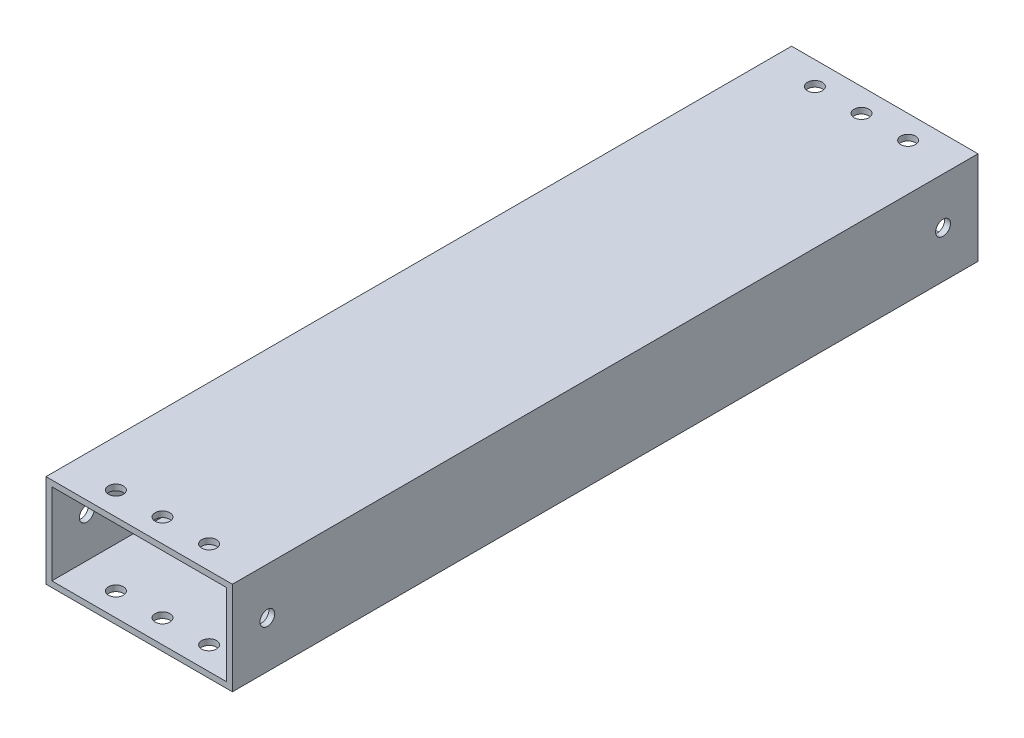
SolidWorks part; units mm, degrees
ref_plane "Front Plane" through (0, 0, 0) normal (0, 0, 1) x (1, 0, 0)
ref_plane "Top Plane" through (0, 0, 0) normal (0, 1, 0) x (1, 0, 0)
ref_plane "Right Plane" through (0, 0, 0) normal (1, 0, 0) x (0, 0, -1)
sketch "Sketch1" plane through (0, 0, 0) normal (0, 0, 1) x (1, 0, 0)
  line L0 (-23.8125, 11.1125) -> (23.8125, 11.1125)
  line L1 (-25.4, -12.7) -> (25.4, -12.7)
  line L2 (-25.4, -12.7) -> (-25.4, 12.7)
  line L3 (-25.4, 12.7) -> (25.4, 12.7)
  line L4 (25.4, -12.7) -> (25.4, 12.7)
  line L5 (-25.4, -12.7) -> (25.4, 12.7) construction
  line L6 (-25.4, 12.7) -> (25.4, -12.7) construction
  line L7 (23.8125, -11.1125) -> (23.8125, 11.1125)
  line L8 (-23.8125, -11.1125) -> (23.8125, -11.1125)
  line L9 (-23.8125, -11.1125) -> (-23.8125, 11.1125)
  point P0 (0, 0)
  dimension "D1" = 50.8
  dimension "D2" = 25.4
  dimension "D3" = 1.5875
extrude "Boss-Extrude1" add sketch "Sketch1" along normal mid plane 203.2
sketch "Sketch2" plane through (25.4, 0, 0) normal (1, 0, 0) x (0, 0, -1)
  line L0 (-101.6, -12.7) -> (-101.6, 12.7) construction
  line L1 (0, 12.7) -> (0, -12.7) construction
  line L2 (-101.6, 12.7) -> (101.6, 12.7) construction
  line L3 (-101.6, -12.7) -> (101.6, -12.7) construction
  circle A0 centre (-92.075, 0) radius 2.0193
  circle A1 centre (92.075, 0) radius 2.0193
  point P10 (0, 0)
  dimension "D2" = 4.0386
  dimension "D1" = 9.525
extrude "Cut-Extrude1" cut sketch "Sketch2" against normal through all
sketch "Sketch3" plane through (0, 12.7, 0) normal (0, 1, 0) x (1, 0, 0)
  line L0 (-25.4, 0) -> (25.4, 0) construction
  line L1 (-25.4, -101.6) -> (-25.4, 101.6) construction
  line L2 (25.4, -101.6) -> (25.4, 101.6) construction
  line L3 (25.4, -101.6) -> (-25.4, -101.6) construction
  circle A0 centre (-12.7, -95.25) radius 2.0193
  circle A1 centre (0, -95.25) radius 2.0193
  circle A2 centre (12.7, -95.25) radius 2.0193
  circle A3 centre (12.7, 95.25) radius 2.0193
  circle A4 centre (0, 95.25) radius 2.0193
  circle A5 centre (-12.7, 95.25) radius 2.0193
  point P12 (0, 0)
  point P16 (0, 0)
  dimension "D1" = 4.0386
  dimension "D2" = 12.7
  dimension "D3" = 12.7
  dimension "D4" = 6.35
extrude "Cut-Extrude2" cut sketch "Sketch3" against normal through all
